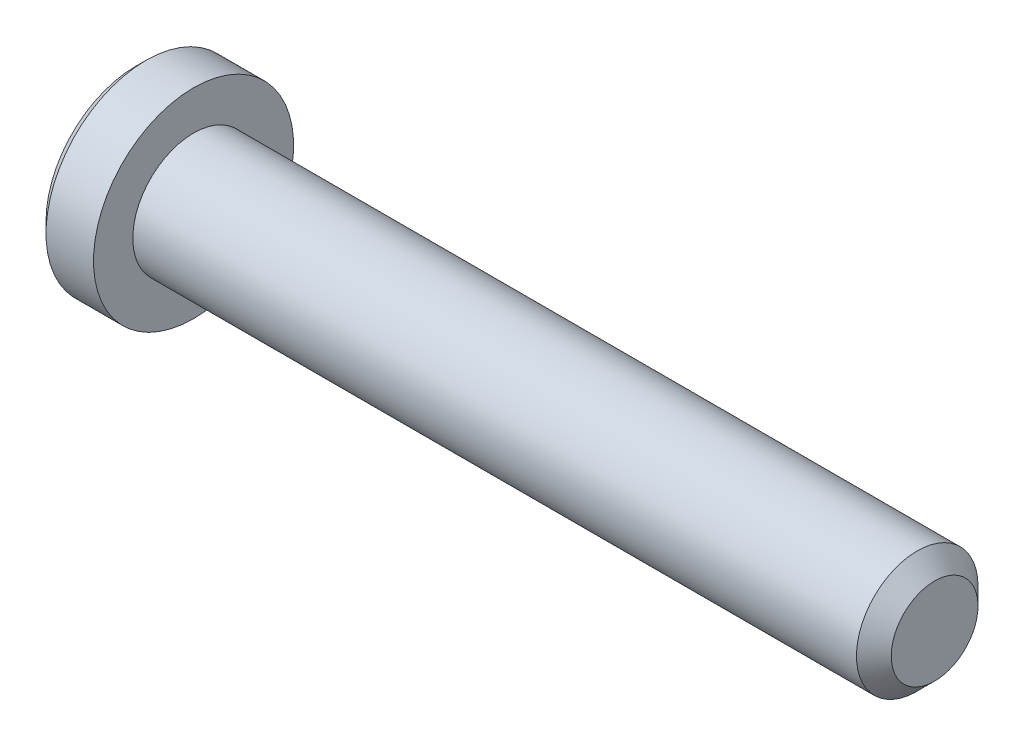
SolidWorks part; units mm, degrees
ref_plane "Front Plane" through (0, 0, 0) normal (0, 0, 1) x (1, 0, 0)
ref_plane "Top Plane" through (0, 0, 0) normal (0, 1, 0) x (1, 0, 0)
ref_plane "Right Plane" through (0, 0, 0) normal (1, 0, 0) x (0, 0, -1)
sketch "Sketch1" plane through (0, 0, 0) normal (0, 0, 1) x (1, 0, 0)
  line L0 (12.7, 0) -> (-12.7, 0) construction
  line L1 (12.7, 2.0828) -> (12.7, -2.0828) construction
  line L2 (-12.7, 3.429) -> (-12.7, -3.429) construction
  line L3 (-12.7, 3.429) -> (-14.3288, 3.429) construction
  line L4 (-14.3288, 3.429) -> (-14.6844, 3.0734) construction
  line L5 (-14.6844, 3.0734) -> (-14.6844, -3.0734) construction
  line L6 (-14.6844, -3.0734) -> (-14.3288, -3.429) construction
  line L7 (-14.3288, -3.429) -> (-12.7, -3.429) construction
  point P7 (-13.1604, 0)
  point P12 (9.525, -2.0828)
  dimension "D1" = 45
  dimension "Dec." = 4.1656
  dimension "Length" = 25.4
  dimension "Head Dia" = 6.858
  dimension "Head Height" = 1.9844
  dimension "Hex Depth" = 1.524
  dimension "Chamfer" = 0.3556
  dimension "D2" = 3.175
ref_plane "Plane1" through (12.7, 0, 0) normal (1, 0, 0) x (0, 0, -1)
ref_plane "Plane2" through (-14.6844, 0, 0) normal (1, 0, 0) x (0, 0, -1)
sketch "Sketch2" plane through (12.7, 0, 0) normal (1, 0, 0) x (0, 0, -1)
  circle A0 centre (0, 0) radius 2.0828
extrude "Boss-Extrude1" add sketch "Sketch2" against normal up to vertex (25.4 mm away) up to point (-12.7, 0, 0)
sketch "Sketch3" plane through (12.7, 0, 0) normal (1, 0, 0) x (0, 0, -1)
  circle A0 centre (0, 0) radius 2.0828 construction
  circle A1 centre (0, 0) radius 2.0828
curve "Helix/Spiral1" pitch 0.7937 height 26.1937 turns 33 parameters "Pitch"=0.7937
chamfer "Chamfer1" distance 0.5953 angle 45 1 edges at (12.7, 0, -2.0828)
sketch "Sketch5" plane through (0, 0, 0) normal (0, 0, 1) x (1, 0, 0)
  line L0 (12.3527, 2.0828) -> (13.0473, 2.0828)
  line L1 (13.0473, 2.0828) -> (12.7496, 1.5672)
  line L2 (12.7496, 1.5672) -> (12.6504, 1.5672)
  line L3 (12.6504, 1.5672) -> (12.3527, 2.0828)
  line L4 (12.7, 1.5672) -> (12.7, 2.0828) construction
  line L5 (12.5016, 1.825) -> (12.8984, 1.825) construction
  dimension "D1" = 60
  dimension "D2" = 0.3969
  dimension "D3" = 0.0992
sweep "Cut-Sweep1" [suppressed] cut profiles "Sketch5" path "Helix/Spiral1"
sketch "Sketch4" plane through (-14.6844, 0, 0) normal (1, 0, 0) x (0, 0, -1)
  line L0 (-3.429, 0.7937) -> (3.429, 0.7937) construction
  line L1 (0, 1.1457) -> (-0.9922, 0.5728)
  line L2 (-0.9922, 0.5728) -> (-0.9922, -0.5728)
  line L3 (-0.9922, -0.5728) -> (0, -1.1457)
  line L4 (0, -1.1457) -> (0.9922, -0.5728)
  line L5 (0.9922, -0.5728) -> (0.9922, 0.5728)
  line L6 (0.9922, 0.5728) -> (0, 1.1457)
  line L7 (0, 0) -> (0, 0.7937) construction
  circle A0 centre (0, 0) radius 0.9922 construction
  dimension "Hex Size" = 1.9844
  dimension "D1" = 6.858
  dimension "D2" = 0.7937
sketch "Sketch6" plane through (0, 0, 0) normal (0, 0, 1) x (1, 0, 0)
  line L0 (-14.3288, 3.429) -> (-14.6844, 3.0734) construction
  line L1 (-12.7, 3.429) -> (-14.3288, 3.429) construction
  line L2 (-12.7, 3.429) -> (-12.7, -3.429) construction
  line L3 (-14.6844, 3.0734) -> (-14.6844, -3.0734) construction
  line L4 (-14.3288, 3.429) -> (-14.6844, 3.0734)
  line L5 (-12.7, 3.429) -> (-14.3288, 3.429)
  line L6 (-12.7, 3.429) -> (-12.7, 0)
  line L7 (-14.6844, 3.0734) -> (-14.6844, 0)
  line L8 (-12.7, 0) -> (-14.6844, 0) construction
  line L9 (-12.7, 0) -> (-14.6844, 0)
revolve "Revolve1" add sketch "Sketch6" angle 360 about L8
extrude "Cut-Extrude1" cut sketch "Sketch4" along normal up to vertex (1.524 mm away) up to point (-13.1604, 0, 0)
sketch "Sketch8" plane through (-14.6844, 0, 0) normal (-1, 0, 0) x (0, 0, 1)
  circle A1 centre (0, 0) radius 1.1457
extrude "Cut-Extrude2" cut sketch "Sketch8" against normal through all draft 45
equation "\"D3@Helix/Spiral1\" = \"Length@Sketch1\"+\"Pitch@Helix/Spiral1\""
equation "\"D3@Sketch5\" = \"Pitch@Helix/Spiral1\"*.125"
equation "\"D2@Sketch5\" = \"Pitch@Helix/Spiral1\"*.50"
equation "\"D1@Chamfer1\" = \"Pitch@Helix/Spiral1\"*.75"
equation "\"D2@Sketch1\" = \"Pitch@Helix/Spiral1\"*4"
equation "\"D1@Sketch4\" = \"Head Dia@Sketch1\""
